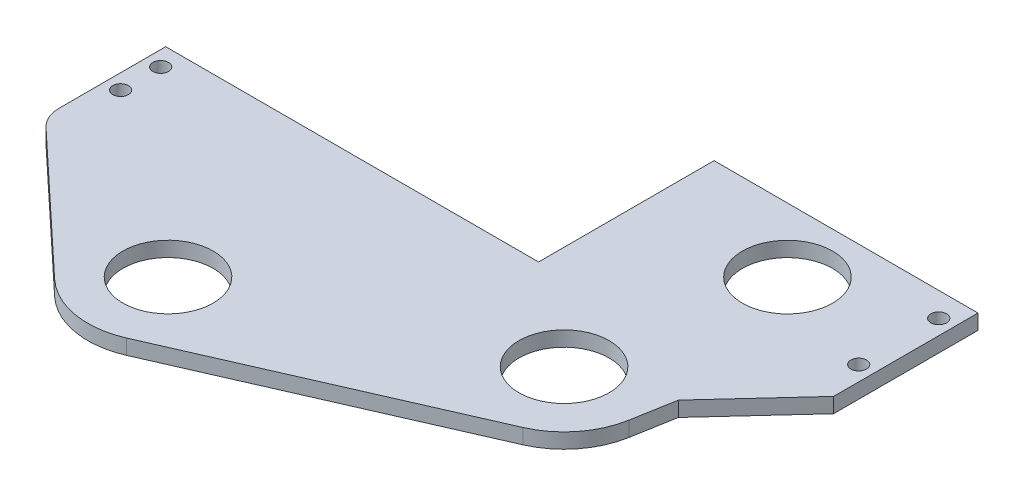
SolidWorks part; units mm, degrees
ref_plane "Front Plane" through (0, 0, 0) normal (0, 0, 1) x (1, 0, 0)
ref_plane "Top Plane" through (0, 0, 0) normal (0, 1, 0) x (1, 0, 0)
ref_plane "Right Plane" through (0, 0, 0) normal (1, 0, 0) x (0, 0, -1)
sketch "Sketch1" plane through (0, 0, 0) normal (0, 1, 0) x (1, 0, 0)
  line L1 (-62.0695, -79.8953) -> (25.163, -41.6958)
  line L5 (39.9361, -22.8907) -> (42.2711, -9.5867)
  line L6 (42.2711, -9.5867) -> (65.827, 16.0128)
  line L12 (-135.7857, -31.9357) -> (-135.7857, 6.1643)
  line L16 (-135.7857, 6.1643) -> (-17.7344, 6.1643)
  line L17 (-135.7857, -31.9357) -> (-89.6201, -75.1681)
  line L19 (65.8268, 61.7268) -> (-17.7344, 61.7268)
  line L20 (65.827, 16.0128) -> (65.8268, 61.7268)
  line L22 (-17.7344, 61.7268) -> (-17.7344, 6.1643)
  circle A0 centre (25.8218, 41.4126) radius 14.29
  circle A1 centre (15.0126, -18.5165) radius 14.29
  circle A2 centre (-72.2583, -56.6285) radius 14.29
  arc A4 (39.9361, -22.8907) -> (25.163, -41.6958) centre (15.0127, -18.5164) cw
  arc A6 (-62.0695, -79.8953) -> (-89.6201, -75.1681) centre (-72.2582, -56.6283) cw
  point P11 (-62.0695, -79.8953)
extrude "Boss-Extrude1" add sketch "Sketch1" along normal blind 4.7625
fillet "Fillet1" radius 10 1 edges at (-135.7857, 2.3813, 31.9357)
hole_wizard "#10 Clearance Hole1" positions "Sketch2" profile "Sketch3" hole size "#10" standard "ANSI Inch" end condition through all
sketch "Sketch2" plane through (0, 4.7625, 0) normal (0, 1, 0) x (1, 0, 0)
  point P0 (61.0644, 54.0575)
  point P3 (61.0644, 28.7127)
  point P7 (-131.0232, -0.1857)
  point P10 (-131.0232, -12.8857)
sketch "Sketch3" plane through (61.0644, 4.7625, -54.0575) normal (1, 0, 0) x (0, 0, 1)
  line L0 (0, 0) -> (0, 4.7625)
  line L1 (0, 4.7625) -> (2.4892, 4.7625)
  line L2 (2.4892, 4.7625) -> (2.4892, 0)
  line L5 (2.4892, 0) -> (0, 0)
  line L11 (0, -6.35) -> (0, 107.95) construction
  dimension "Thru Hole Dia." = 4.9784
  dimension "Thru Hole Depth" = 4.7625
